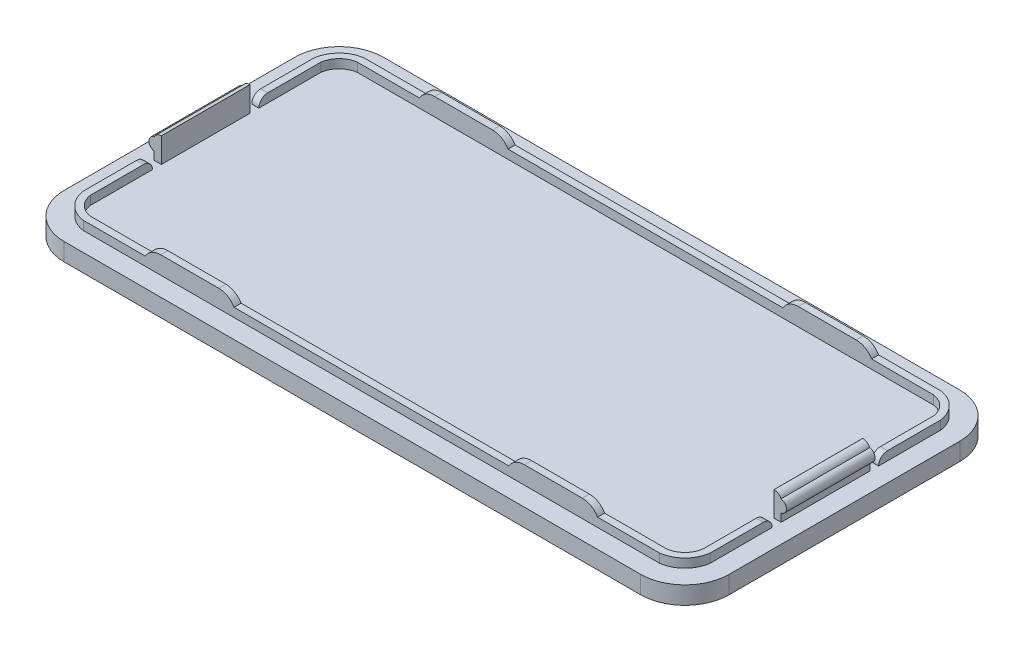
SolidWorks part; units mm, degrees
ref_plane "前视基准面" through (0, 0, 0) normal (0, 0, 1) x (1, 0, 0)
ref_plane "上视基准面" through (0, 0, 0) normal (0, 1, 0) x (1, 0, 0)
ref_plane "右视基准面" through (0, 0, 0) normal (1, 0, 0) x (0, 0, -1)
sketch "zero" plane through (0, 0, 0) normal (0, 1, 0) x (1, 0, 0)
  line L1 (-29.5, 15) -> (29.5, 15)
  line L2 (-32.5, 12) -> (-32.5, -12)
  line L3 (-29.5, -15) -> (29.5, -15)
  line L4 (32.5, 12) -> (32.5, -12)
  line L5 (-32.5, 15) -> (32.5, -15) construction
  line L6 (-32.5, -15) -> (32.5, 15) construction
  line L7 (-25.7, -15) -> (-14.5, -15)
  line L8 (-25.7, -15) -> (-25.7, -9.6569)
  line L9 (-25.7, -9.6569) -> (-14.5, -9.6569)
  line L10 (-14.5, -15) -> (-14.5, -9.6569)
  line L11 (5.2, -15) -> (12.7, -15)
  line L12 (5.2, -15) -> (5.2, -11)
  line L13 (5.2, -11) -> (12.7, -11)
  line L14 (12.7, -15) -> (12.7, -11)
  line L15 (17.8, -15) -> (25.3, -15)
  line L16 (17.8, -15) -> (17.8, -11)
  line L17 (17.8, -11) -> (25.3, -11)
  line L18 (25.3, -15) -> (25.3, -11)
  line L19 (-32.5, 7.7) -> (-19.5, 7.7)
  line L20 (-32.5, 7.7) -> (-32.5, -4.3)
  line L21 (-32.5, -4.3) -> (-19.5, -4.3)
  line L22 (-19.5, 7.7) -> (-19.5, -4.3)
  line L23 (-25.5, 14) -> (25.5, 14)
  line L24 (-25.5, 14) -> (-25.5, 8.8)
  line L25 (-25.5, 8.8) -> (25.5, 8.8)
  line L26 (25.5, 14) -> (25.5, 8.8)
  line L27 (-19.5, 7.2329) -> (-35.5, 7.2329)
  line L28 (-19.5, 7.2329) -> (-19.5, -3.7671)
  line L29 (-19.5, -3.7671) -> (-35.5, -3.7671)
  line L30 (-35.5, 7.2329) -> (-35.5, -3.7671)
  arc A0 (29.5, -15) -> (32.5, -12) centre (29.5, -12) ccw
  arc A1 (29.5, 15) -> (32.5, 12) centre (29.5, 12) cw
  arc A2 (-32.5, -12) -> (-29.5, -15) centre (-29.5, -12) ccw
  arc A3 (-29.5, 15) -> (-32.5, 12) centre (-29.5, 12) ccw
  circle A4 centre (-29, 11.4) radius 3
  circle A5 centre (-29, -11.5) radius 3
  circle A6 centre (29, 11.4) radius 3
  circle A7 centre (29, -11.5) radius 3
  circle A8 centre (-29, 11.4) radius 1.375
  circle A9 centre (-29, -11.5) radius 1.375
  circle A10 centre (29, -11.5) radius 1.375
  circle A11 centre (29, 11.4) radius 1.375
  point P0 (0, 0)
  dimension "D3" = 3
  dimension "D4" = 6
  dimension "D9" = 2.75
  dimension "D1" = 65
  dimension "D2" = 30
  dimension "D5" = 3.6
  dimension "D6" = 3.5
  dimension "D7" = 3.5
  dimension "D8" = 3.5
  dimension "D10" = 12
  dimension "D11" = 7.3
  dimension "D12" = 13
  dimension "D13" = 11.2
  dimension "D14" = 6.8
  dimension "D15" = 19.7
  dimension "D16" = 7.5
  dimension "D17" = 7.5
  dimension "D18" = 5.1
  dimension "D19" = 4
  dimension "D20" = 5.2
  dimension "D21" = 7
  dimension "D22" = 7
  dimension "D23" = 1
  dimension "D24" = 11
  dimension "D25" = 16
sketch "sugar" plane through (0, 0, 0) normal (0, 1, 0) x (1, 0, 0)
  line L1 (-29.5, 15) -> (29.5, 15)
  line L2 (-32.5, 12) -> (-32.5, -12)
  line L3 (-29.5, -15) -> (29.5, -15)
  line L4 (32.5, 12) -> (32.5, -12)
  line L5 (-32.5, 15) -> (32.5, -15) construction
  line L6 (-32.5, -15) -> (32.5, 15) construction
  line L7 (23.5, -11.5) -> (19.5, -11.5)
  line L8 (23.5, -11.5) -> (23.5, -13.9082)
  line L9 (23.5, -13.9082) -> (19.5, -13.9082)
  line L10 (19.5, -11.5) -> (19.5, -13.9082)
  line L11 (16, -11.0071) -> (8.5, -11.0071)
  line L12 (16, -11.0071) -> (16, -15)
  line L13 (16, -15) -> (8.5, -15)
  line L14 (8.5, -11.0071) -> (8.5, -15)
  line L15 (20.5, -13.9082) -> (22.5, -13.9082)
  line L16 (20.5, -13.9082) -> (20.5, -14.8173)
  line L17 (20.5, -14.8173) -> (22.5, -14.8173)
  line L18 (22.5, -13.9082) -> (22.5, -14.8173)
  arc A0 (29.5, 15) -> (32.5, 12) centre (29.5, 12) cw
  arc A1 (29.5, -15) -> (32.5, -12) centre (29.5, -12) ccw
  arc A2 (-32.5, -12) -> (-29.5, -15) centre (-29.5, -12) ccw
  arc A3 (-29.5, 15) -> (-32.5, 12) centre (-29.5, 12) ccw
  circle A4 centre (-29, 11.4) radius 3
  circle A5 centre (-29, 11.4) radius 1.375
  circle A6 centre (-29, -11.5) radius 3
  circle A7 centre (-29, -11.5) radius 1.375
  circle A8 centre (29, 11.4) radius 3
  circle A9 centre (29, 11.4) radius 1.375
  circle A10 centre (29, -11.5) radius 3
  circle A11 centre (29, -11.5) radius 1.375
  dimension "D3" = 3
  dimension "D1" = 65
  dimension "D2" = 30
  dimension "D4" = 9
  dimension "D5" = 4
  dimension "D6" = 3.5
  dimension "D7" = 7.5
  dimension "D8" = 2
  dimension "D9" = 1
sketch "case" plane through (0, 0, 0) normal (0, 1, 0) x (1, 0, 0)
  line L1 (-34.0422, 18) -> (30.9578, 18)
  line L2 (-39.0422, 13) -> (-39.0422, -13)
  line L3 (-34.0422, -18) -> (30.9578, -18)
  line L4 (35.9578, 13) -> (35.9578, -13)
  line L5 (-39.0422, 18) -> (35.9578, -18) construction
  line L6 (-39.0422, -18) -> (35.9578, 18) construction
  arc A0 (-39.0422, -13) -> (-34.0422, -18) centre (-34.0422, -13) ccw
  arc A1 (30.9578, -18) -> (35.9578, -13) centre (30.9578, -13) ccw
  arc A2 (30.9578, 18) -> (35.9578, 13) centre (30.9578, 13) cw
  arc A3 (-34.0422, 18) -> (-39.0422, 13) centre (-34.0422, 13) ccw
  point P0 (-1.5422, 0)
  point P3 (-1.5422, 0)
  dimension "D3" = 5
  dimension "D1" = 75
  dimension "D2" = 36
extrude "凸台-拉伸2" add sketch "case" along normal blind 2
sketch "草图2" plane through (0, 0, 0) normal (0, 1, 0) x (1, 0, 0)
  line L0 (-39.0422, 13) -> (-39.0422, -13) construction
  line L1 (30.9578, 18) -> (-34.0422, 18) construction
  line L4 (-34.0422, -15.05) -> (30.9578, -15.05)
  line L5 (33.0078, -13) -> (33.0078, 13)
  line L6 (30.9578, 15.05) -> (-34.0422, 15.05)
  line L7 (-36.0922, 13) -> (-36.0922, -13)
  line L12 (33.8078, -13) -> (33.8078, 13)
  line L13 (30.9578, 15.85) -> (-34.0422, 15.85)
  line L14 (-36.8922, 13) -> (-36.8922, -13)
  line L15 (-34.0422, -15.85) -> (30.9578, -15.85)
  arc A4 (30.9578, -15.05) -> (33.0078, -13) centre (30.6303, -12.6725) ccw
  arc A5 (33.0078, 13) -> (30.9578, 15.05) centre (30.6303, 12.6725) ccw
  arc A6 (-34.0422, 15.05) -> (-36.0922, 13) centre (-33.7147, 12.6725) ccw
  arc A7 (-36.0922, -13) -> (-34.0422, -15.05) centre (-33.7147, -12.6725) ccw
  arc A12 (30.9578, -15.85) -> (33.8078, -13) centre (30.535, -12.5772) ccw
  arc A13 (33.8078, 13) -> (30.9578, 15.85) centre (30.535, 12.5772) ccw
  arc A14 (-34.0422, 15.85) -> (-36.8922, 13) centre (-33.6194, 12.5772) ccw
  arc A15 (-36.8922, -13) -> (-34.0422, -15.85) centre (-33.6194, -12.5772) ccw
ref_plane "基准面1" through (0, 2, 0) normal (0, 1, 0) x (1, 0, 0)
sketch "草图3" plane through (0, 2, 0) normal (0, 1, 0) x (1, 0, 0)
  line L4 (-34.0422, -15.05) -> (30.9578, -15.05)
  line L5 (33.0078, -13) -> (33.0078, 13)
  line L6 (30.9578, 15.05) -> (-34.0422, 15.05)
  line L7 (-36.0922, 13) -> (-36.0922, -13)
  line L8 (-34.0422, -15.05) -> (30.9578, -15.05)
  line L9 (33.0078, -13) -> (33.0078, 13)
  line L10 (30.9578, 15.05) -> (-34.0422, 15.05)
  line L11 (-36.0922, 13) -> (-36.0922, -13)
  line L12 (-36.8922, 13) -> (-36.8922, -13)
  line L13 (-34.0422, -15.85) -> (30.9578, -15.85)
  line L14 (33.8078, -13) -> (33.8078, 13)
  line L15 (30.9578, 15.85) -> (-34.0422, 15.85)
  line L16 (-36.8922, 13) -> (-36.8922, -13)
  line L17 (-34.0422, -15.85) -> (30.9578, -15.85)
  line L18 (33.8078, -13) -> (33.8078, 13)
  line L19 (30.9578, 15.85) -> (-34.0422, 15.85)
  arc A4 (30.9578, -15.05) -> (33.0078, -13) centre (30.6303, -12.6725) ccw
  arc A5 (33.0078, 13) -> (30.9578, 15.05) centre (30.6303, 12.6725) ccw
  arc A6 (-34.0422, 15.05) -> (-36.0922, 13) centre (-33.7147, 12.6725) ccw
  arc A7 (-36.0922, -13) -> (-34.0422, -15.05) centre (-33.7147, -12.6725) ccw
  arc A8 (30.9578, -15.05) -> (33.0078, -13) centre (30.6303, -12.6725) ccw
  arc A9 (33.0078, 13) -> (30.9578, 15.05) centre (30.6303, 12.6725) ccw
  arc A10 (-34.0422, 15.05) -> (-36.0922, 13) centre (-33.7147, 12.6725) ccw
  arc A11 (-36.0922, -13) -> (-34.0422, -15.05) centre (-33.7147, -12.6725) ccw
  arc A12 (-36.8922, -13) -> (-34.0422, -15.85) centre (-33.6194, -12.5772) ccw
  arc A13 (30.9578, -15.85) -> (33.8078, -13) centre (30.535, -12.5772) ccw
  arc A14 (33.8078, 13) -> (30.9578, 15.85) centre (30.535, 12.5772) ccw
  arc A15 (-34.0422, 15.85) -> (-36.8922, 13) centre (-33.6194, 12.5772) ccw
  arc A16 (-36.8922, -13) -> (-34.0422, -15.85) centre (-33.6194, -12.5772) ccw
  arc A17 (30.9578, -15.85) -> (33.8078, -13) centre (30.535, -12.5772) ccw
  arc A18 (33.8078, 13) -> (30.9578, 15.85) centre (30.535, 12.5772) ccw
  arc A19 (-34.0422, 15.85) -> (-36.8922, 13) centre (-33.6194, 12.5772) ccw
  dimension "D1" = 0
  dimension "D2" = 0
extrude "凸台-拉伸4" add sketch "草图3" along normal blind 1
ref_plane "基准面3" through (33.8078, 0, 0) normal (1, 0, 0) x (0, 0, -1)
sketch "草图7" plane through (0, 2, 0) normal (0, 1, 0) x (1, 0, 0)
  line L0 (-36.8922, 13) -> (-36.8922, -13) construction
  line L1 (-36.8922, 5) -> (-36.0922, 5)
  line L2 (-36.8922, 5) -> (-36.8922, -5)
  line L3 (-36.8922, -5) -> (-36.0922, -5)
  line L4 (-36.0922, 5) -> (-36.0922, -5)
  line L5 (-36.0922, 13) -> (-36.0922, -13) construction
  point P10 (-36.0922, 0)
  dimension "D1" = 5
  dimension "D2" = 10
extrude "凸台-拉伸8" add sketch "草图7" along normal blind 2.8
ref_plane "基准面5" through (0, 0, 5) normal (0, 0, 1) x (1, 0, 0)
sketch "草图8" plane through (0, 0, 5) normal (0, 0, 1) x (1, 0, 0)
  line L0 (-34.0422, 2) -> (-39.0422, 2) construction
  line L1 (-36.8922, 4.8) -> (-36.8922, 3) construction
  circle A0 centre (-36.7922, 3.6) radius 0.7
  dimension "D1" = 1.4
  dimension "D2" = 1.6
  dimension "D3" = 0.1
extrude "凸台-拉伸9" add sketch "草图8" against normal blind 10
fillet "圆角1" radius 0.85 1 edges at (-36.8922, 4.8, 0)
ref_plane "基准面7" through (-36.8922, 0, 0) normal (-1, 0, 0) x (0, 0, 1)
sketch "草图11" plane through (-36.8922, 0, 0) normal (-1, 0, 0) x (0, 0, 1)
  line L0 (-13, 2) -> (13, 2) construction
  line L1 (5, 3) -> (6, 3)
  line L2 (5, 3) -> (5, 2)
  line L3 (5, 2) -> (6, 2)
  line L4 (6, 3) -> (6, 2)
  line L6 (-5, 3) -> (-6, 3)
  line L7 (-5, 3) -> (-5, 2)
  line L8 (-5, 2) -> (-6, 2)
  line L9 (-6, 3) -> (-6, 2)
  dimension "D1" = 1
  dimension "D2" = 1
extrude "切除-拉伸1" cut sketch "草图11" against normal blind 1.2
fillet "圆角2" radius 1 2 edges at (-36.4922, 3, 6) (-36.4922, 3, -6)
ref_plane "基准面8" through (0, 0, 0) normal (0, -1, 0) x (-1, 0, 0)
sketch "草图13" plane through (0, 3, 0) normal (0, 1, 0) x (1, 0, 0)
  line L0 (33.0078, -13) -> (33.0078, 13) construction
  line L1 (33.0078, 5) -> (33.8078, 5)
  line L2 (33.0078, 5) -> (33.0078, -5)
  line L3 (33.0078, -5) -> (33.8078, -5)
  line L4 (33.8078, 5) -> (33.8078, -5)
  line L5 (33.8078, -13) -> (33.8078, 13) construction
  line L7 (35.9578, -13) -> (35.9578, 13) construction
  point P12 (35.9578, 0)
  point P13 (33.8078, 0)
  dimension "D1" = 10
extrude "凸台-拉伸10" add sketch "草图13" along normal blind 1.8
sketch "草图14" plane through (0, 0, 5) normal (0, 0, 1) x (1, 0, 0)
  line L0 (33.8078, 2) -> (30.9578, 2) construction
  line L1 (33.8078, 4.8) -> (33.8078, 3) construction
  circle A0 centre (33.7078, 3.6) radius 0.7
  dimension "D2" = 1.4
  dimension "D1" = 1.6
  dimension "D3" = 0.1
extrude "凸台-拉伸11" add sketch "草图14" against normal blind 10
fillet "圆角3" radius 0.85 1 edges at (33.8078, 4.8, 0)
sketch "草图15" plane through (0, 3, 0) normal (0, 1, 0) x (1, 0, 0)
  line L0 (33.8078, 5) -> (33.8078, 13) construction
  line L1 (33.0078, 5) -> (33.8078, 5)
  line L2 (33.0078, 5) -> (33.0078, 6)
  line L3 (33.0078, 6) -> (33.8078, 6)
  line L4 (33.8078, 5) -> (33.8078, 6)
  line L5 (33.8078, -13) -> (33.8078, -5) construction
  line L6 (33.0078, -5) -> (33.8078, -5)
  line L7 (33.0078, -5) -> (33.0078, -6)
  line L8 (33.0078, -6) -> (33.8078, -6)
  line L9 (33.8078, -5) -> (33.8078, -6)
  dimension "D1" = 1
  dimension "D2" = 1
extrude "切除-拉伸3" cut sketch "草图15" against normal blind 1
fillet "圆角4" radius 1 2 edges at (33.4078, 3, 6) (33.4078, 3, -6)
sketch "草图16" plane through (0, 2, 0) normal (0, 1, 0) x (1, 0, 0)
  line L4 (-34.0422, -15.05) -> (30.9578, -15.05)
  line L5 (33.0078, -13) -> (33.0078, 13)
  line L6 (30.9578, 15.05) -> (-34.0422, 15.05)
  line L7 (-36.0922, 13) -> (-36.0922, -13)
  line L8 (-34.0422, -15.05) -> (30.9578, -15.05)
  line L9 (33.0078, -13) -> (33.0078, 13)
  line L10 (30.9578, 15.05) -> (-34.0422, 15.05)
  line L11 (-36.0922, 13) -> (-36.0922, -13)
  arc A4 (30.9578, -15.05) -> (33.0078, -13) centre (30.6303, -12.6725) ccw
  arc A5 (33.0078, 13) -> (30.9578, 15.05) centre (30.6303, 12.6725) ccw
  arc A6 (-34.0422, 15.05) -> (-36.0922, 13) centre (-33.7147, 12.6725) ccw
  arc A7 (-36.0922, -13) -> (-34.0422, -15.05) centre (-33.7147, -12.6725) ccw
  arc A8 (30.9578, -15.05) -> (33.0078, -13) centre (30.6303, -12.6725) ccw
  arc A9 (33.0078, 13) -> (30.9578, 15.05) centre (30.6303, 12.6725) ccw
  arc A10 (-34.0422, 15.05) -> (-36.0922, 13) centre (-33.7147, 12.6725) ccw
  arc A11 (-36.0922, -13) -> (-34.0422, -15.05) centre (-33.7147, -12.6725) ccw
  dimension "D1" = 0
extrude "凸台-拉伸12" add sketch "草图2" against normal blind 2
sketch "草图20" plane through (0, 0, 0) normal (0, -1, 0) x (1, 0, 0)
  line L4 (30.9578, 15.85) -> (-34.0422, 15.85)
  line L5 (-36.8922, 13) -> (-36.8922, -13)
  line L6 (-34.0422, -15.85) -> (30.9578, -15.85)
  line L8 (30.9578, 15.85) -> (-34.0422, 15.85)
  line L10 (-34.0422, -15.85) -> (30.9578, -15.85)
  line L12 (-36.0922, 13) -> (-36.0922, -13)
  line L13 (-34.0422, -15.05) -> (30.9578, -15.05)
  line L14 (33.0078, -13) -> (33.0078, 13)
  line L15 (30.9578, 15.05) -> (-34.0422, 15.05)
  line L16 (-36.0922, 13) -> (-36.0922, -13)
  line L17 (-34.0422, -15.05) -> (30.9578, -15.05)
  line L18 (33.0078, -13) -> (33.0078, 13)
  line L19 (30.9578, 15.05) -> (-34.0422, 15.05)
  line L20 (-36.8922, 13) -> (-36.8922, -13)
  line L21 (33.8078, -13) -> (33.8078, 13)
  line L22 (33.8078, -13) -> (33.8078, 13)
  arc A4 (33.8078, 13) -> (30.9578, 15.85) centre (30.535, 12.5772) ccw
  arc A5 (-34.0422, 15.85) -> (-36.8922, 13) centre (-33.6194, 12.5772) ccw
  arc A6 (-36.8922, -13) -> (-34.0422, -15.85) centre (-33.6194, -12.5772) ccw
  arc A7 (30.9578, -15.85) -> (33.8078, -13) centre (30.535, -12.5772) ccw
  arc A8 (33.8078, 13) -> (30.9578, 15.85) centre (30.535, 12.5772) ccw
  arc A9 (-34.0422, 15.85) -> (-36.8922, 13) centre (-33.6194, 12.5772) ccw
  arc A10 (-36.8922, -13) -> (-34.0422, -15.85) centre (-33.6194, -12.5772) ccw
  arc A11 (30.9578, -15.85) -> (33.8078, -13) centre (30.535, -12.5772) ccw
  arc A12 (-36.0922, -13) -> (-34.0422, -15.05) centre (-33.7147, -12.6725) ccw
  arc A13 (30.9578, -15.05) -> (33.0078, -13) centre (30.6303, -12.6725) ccw
  arc A14 (33.0078, 13) -> (30.9578, 15.05) centre (30.6303, 12.6725) ccw
  arc A15 (-34.0422, 15.05) -> (-36.0922, 13) centre (-33.7147, 12.6725) ccw
  arc A16 (-36.0922, -13) -> (-34.0422, -15.05) centre (-33.7147, -12.6725) ccw
  arc A17 (30.9578, -15.05) -> (33.0078, -13) centre (30.6303, -12.6725) ccw
  arc A18 (33.0078, 13) -> (30.9578, 15.05) centre (30.6303, 12.6725) ccw
  arc A19 (-34.0422, 15.05) -> (-36.0922, 13) centre (-33.7147, 12.6725) ccw
  dimension "D1" = 0
  dimension "D2" = 0
extrude "切除-拉伸4" cut sketch "草图20" along normal blind 2
sketch "草图22" plane through (0, 3, 0) normal (0, 1, 0) x (1, 0, 0)
  line L0 (30.9578, 15.85) -> (-34.0422, 15.85) construction
  line L1 (-27.0422, 15.85) -> (-17.0422, 15.85)
  line L2 (-27.0422, 15.85) -> (-27.0422, 15.05)
  line L3 (-27.0422, 15.05) -> (-17.0422, 15.05)
  line L4 (-17.0422, 15.85) -> (-17.0422, 15.05)
  line L5 (30.9578, 15.05) -> (-34.0422, 15.05) construction
  line L6 (-34.0422, -15.05) -> (30.9578, -15.05) construction
  line L7 (13.9578, 15.85) -> (23.9578, 15.85)
  line L8 (13.9578, 15.85) -> (13.9578, 15.05)
  line L9 (13.9578, 15.05) -> (23.9578, 15.05)
  line L10 (23.9578, 15.85) -> (23.9578, 15.05)
  line L11 (-27.0422, -15.05) -> (-17.0422, -15.05)
  line L12 (-27.0422, -15.05) -> (-27.0422, -15.85)
  line L13 (-27.0422, -15.85) -> (-17.0422, -15.85)
  line L14 (-17.0422, -15.05) -> (-17.0422, -15.85)
  line L15 (-34.0422, -15.85) -> (30.9578, -15.85) construction
  line L16 (35.9578, -13) -> (35.9578, 13) construction
  line L17 (13.9578, -15.05) -> (23.9578, -15.05)
  line L18 (13.9578, -15.05) -> (13.9578, -15.85)
  line L19 (13.9578, -15.85) -> (23.9578, -15.85)
  line L20 (23.9578, -15.05) -> (23.9578, -15.85)
  line L21 (-39.0422, 13) -> (-39.0422, -13) construction
  dimension "D1" = 10
  dimension "D2" = 10
  dimension "D3" = 10
  dimension "D4" = 10
  dimension "D5" = 12
  dimension "D6" = 12
  dimension "D7" = 12
  dimension "D8" = 12
extrude "凸台-拉伸16" add sketch "草图22" along normal blind 1
fillet "圆角5" radius 2 8 edges at (-27.0422, 4, 15.45) (-17.0422, 4, 15.45) (23.9578, 4, 15.45) (13.9578, 4, 15.45) (23.9578, 4, -15.45) (13.9578, 4, -15.45) (-17.0422, 4, -15.45) (-27.0422, 4, -15.45)
sketch "草图23" plane through (0, 0, 0) normal (0, -1, 0) x (1, 0, 0)
  circle A0 centre (30.2578, -11.925) radius 2.3965
  circle A3 centre (22.3078, -11.925) radius 2.3965
  circle A4 centre (14.3578, -11.925) radius 2.3965
  circle A5 centre (6.4078, -11.925) radius 2.3965
  circle A6 centre (-1.5422, -11.925) radius 2.3965
  circle A7 centre (-9.4922, -11.925) radius 2.3965
  circle A8 centre (-17.4422, -11.925) radius 2.3965
  circle A9 centre (-25.3922, -11.925) radius 2.3965
  circle A10 centre (-33.3422, -11.925) radius 2.3965
  circle A11 centre (22.3078, -3.975) radius 2.3965
  circle A12 centre (14.3578, -3.975) radius 2.3965
  circle A13 centre (6.4078, -3.975) radius 2.3965
  circle A14 centre (-1.5422, -3.975) radius 2.3965
  circle A15 centre (-9.4922, -3.975) radius 2.3965
  circle A16 centre (-17.4422, -3.975) radius 2.3965
  circle A17 centre (-25.3922, -3.975) radius 2.3965
  circle A18 centre (-33.3422, -3.975) radius 2.3965
  circle A19 centre (22.3078, 3.975) radius 2.3965
  circle A20 centre (14.3578, 3.975) radius 2.3965
  circle A21 centre (6.4078, 3.975) radius 2.3965
  circle A22 centre (-1.5422, 3.975) radius 2.3965
  circle A23 centre (-9.4922, 3.975) radius 2.3965
  circle A24 centre (-17.4422, 3.975) radius 2.3965
  circle A25 centre (-25.3922, 3.975) radius 2.3965
  circle A26 centre (-33.3422, 3.975) radius 2.3965
  circle A27 centre (22.3078, 11.925) radius 2.3965
  circle A28 centre (14.3578, 11.925) radius 2.3965
  circle A29 centre (6.4078, 11.925) radius 2.3965
  circle A30 centre (-1.5422, 11.925) radius 2.3965
  circle A31 centre (-9.4922, 11.925) radius 2.3965
  circle A32 centre (-17.4422, 11.925) radius 2.3965
  circle A33 centre (-25.3922, 11.925) radius 2.3965
  circle A34 centre (-33.3422, 11.925) radius 2.3965
  circle A35 centre (30.2578, -3.975) radius 2.3965
  circle A36 centre (30.2578, 3.975) radius 2.3965
  circle A37 centre (30.2578, 11.925) radius 2.3965
  dimension "D1" = 9
  dimension "D2" = 4
extrude "凸台-拉伸18" add sketch "草图23" along normal blind 2
fillet "圆角7" radius 0.5 36 edges at (-17.4422, -2, -14.3215) (-9.4922, -2, -14.3215) (-1.5422, -2, -14.3215) (6.4078, -2, -14.3215) (-33.3422, -2, 9.5285) (-33.3422, -2, 1.5785) (-25.3922, -2, 1.5785) (-25.3922, -2, 9.5285) (-17.4422, -2, 9.5285) (-17.4422, -2, 1.5785) (-9.4922, -2, 1.5785) (-9.4922, -2, 9.5285) (-1.5422, -2, 9.5285) (-1.5422, -2, 1.5785) (6.4078, -2, 1.5785) (6.4078, -2, 9.5285) (14.3578, -2, 9.5285) (14.3578, -2, 1.5785) (22.3078, -2, 1.5785) (22.3078, -2, 9.5285) (30.2578, -2, 9.5285) (30.2578, -2, 1.5785) (30.2578, -2, -6.3715) (22.3078, -2, -6.3715) (14.3578, -2, -6.3715) (6.4078, -2, -6.3715) (-1.5422, -2, -6.3715) (-9.4922, -2, -6.3715) (-17.4422, -2, -6.3715) (-25.3922, -2, -6.3715) (-33.3422, -2, -6.3715) (-33.3422, -2, -14.3215) (-25.3922, -2, -14.3215) (14.3578, -2, -14.3215) (22.3078, -2, -14.3215) (30.2578, -2, -14.3215)
